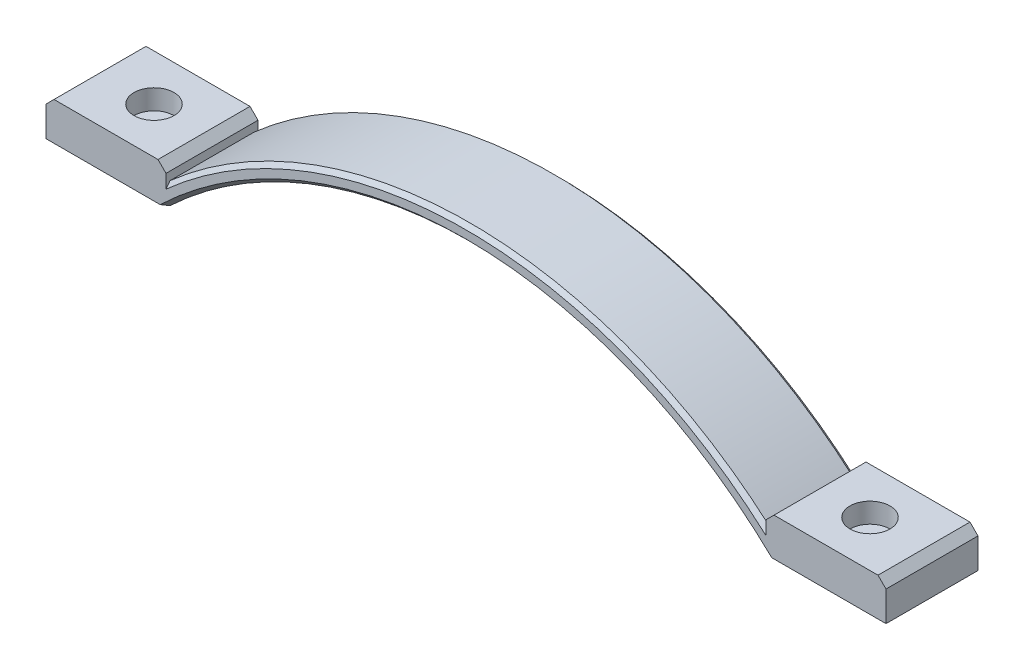
SolidWorks part; units mm, degrees
ref_plane "前视基准面" through (0, 0, 0) normal (0, 0, 1) x (1, 0, 0)
ref_plane "上视基准面" through (0, 0, 0) normal (0, 1, 0) x (1, 0, 0)
ref_plane "右视基准面" through (0, 0, 0) normal (1, 0, 0) x (0, 0, -1)
sketch "草图1" plane through (0, 0, 0) normal (0, 0, 1) x (1, 0, 0)
  line L0 (-113.1726, 0) -> (109.7943, 0) construction
  line L1 (0, 66.0651) -> (0, -77.376) construction
  line L2 (-105, 0) -> (-75, 0)
  line L3 (-105, 0) -> (-105, 9.5)
  line L4 (-105, 9.5) -> (-75, 9.5)
  line L5 (-75, 9.5) -> (-75, 5.4143)
  line L6 (75, 9.5) -> (75, 5.4143)
  line L7 (105, 9.5) -> (75, 9.5)
  line L8 (105, 0) -> (105, 9.5)
  line L9 (105, 0) -> (75, 0)
  arc A0 (75, 0) -> (-75, 0) centre (0, -79.5345) ccw
  arc A1 (75, 5.4143) -> (-75, 5.4143) centre (0, -79.5345) ccw
  dimension "D4" = 4
  dimension "D1" = 9.5
  dimension "D2" = 105
  dimension "D3" = 75
extrude "凸台-拉伸1" add sketch "草图1" along normal blind 11.5 and the other way blind 11.5
sketch "草图2" plane through (0, 9.5, 0) normal (0, 1, 0) x (1, 0, 0)
  line L0 (0, 50.3625) -> (0, -56.7474) construction
  line L1 (-129.0298, 0) -> (119.7088, 0) construction
  circle A0 centre (-89.5, 0) radius 5
  circle A1 centre (89.5, 0) radius 5
  dimension "D1" = 10
  dimension "D2" = 179
extrude "切除-拉伸1" cut sketch "草图2" against normal blind 5
chamfer "倒角1" distance 1 angle 45 4 edges at (0, 29.7849, 11.5) (0, 29.7849, -11.5) (0, 33.7849, -11.5) (0, 33.7849, 11.5)
chamfer "倒角2" distance 2 angle 45 4 edges at (-105, 9.5, 0) (-75, 9.5, 0) (75, 9.5, 0) (105, 9.5, 0)
